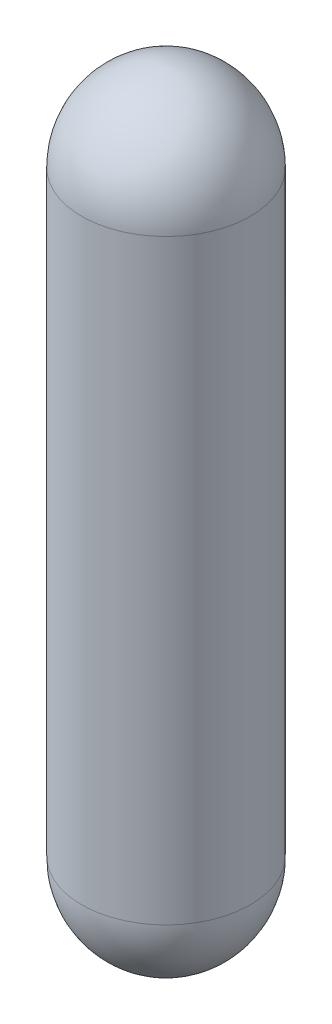
SolidWorks part; units mm, degrees
other "Markup1"
sketch "Sketch2" plane through (-160, -160, 160) normal (0, 0, 1) x (1, 0, 0)
material "Titanium"
ref_plane "Front Plane" through (0, 0, 0) normal (0, 0, 1) x (1, 0, 0)
ref_plane "Top Plane" through (0, 0, 0) normal (0, 1, 0) x (1, 0, 0)
ref_plane "Right Plane" through (0, 0, 0) normal (1, 0, 0) x (0, 0, -1)
sketch "Sketch1" plane through (0, 0, 0) normal (0, 0, 1) x (1, 0, 0)
  line L0 (0, 1768.6324) -> (0, 1771.1724)
  line L2 (0, 0) -> (0, 1542.8) construction
  line L5 (0, -226.2876) -> (0, -228.8276)
  line L6 (0, 738.4774) -> (228.6, 738.4774) construction
  line L7 (215.2638, 1542.8) -> (215.2638, 0)
  line L8 (215.2638, 1096.4433) -> (217.8038, 1096.4433) construction
  line L9 (218.4014, 1542.8) -> (218.4014, 0)
  arc A0 (0, -228.8276) -> (218.4014, 0) centre (-10.1981, -0.4552) ccw
  arc A1 (218.4014, 1542.8) -> (0, 1771.1724) centre (-10.1986, 1542.8) ccw
  arc A2 (215.2638, 1542.8) -> (0, 1768.6324) centre (-10.7962, 1542.8303) ccw
  arc A3 (215.2638, 0) -> (0, -226.2876) centre (-10.7957, -0.4855) cw
  point P19 (0, 0)
  point P20 (4.6838, 1576.3218)
  dimension "D4" = 228.6
  dimension "D5" = 1542.8
  dimension "D6" = 226.06
  dimension "D7" = 226.06
  dimension "D8" = 228.6
  dimension "D1" = 228.6
  dimension "D2" = 2000
  dimension "D3" = 2.54
  dimension "D9" = 228.6
revolve "Revolve1" add sketch "Sketch1" angle 360 about L2
